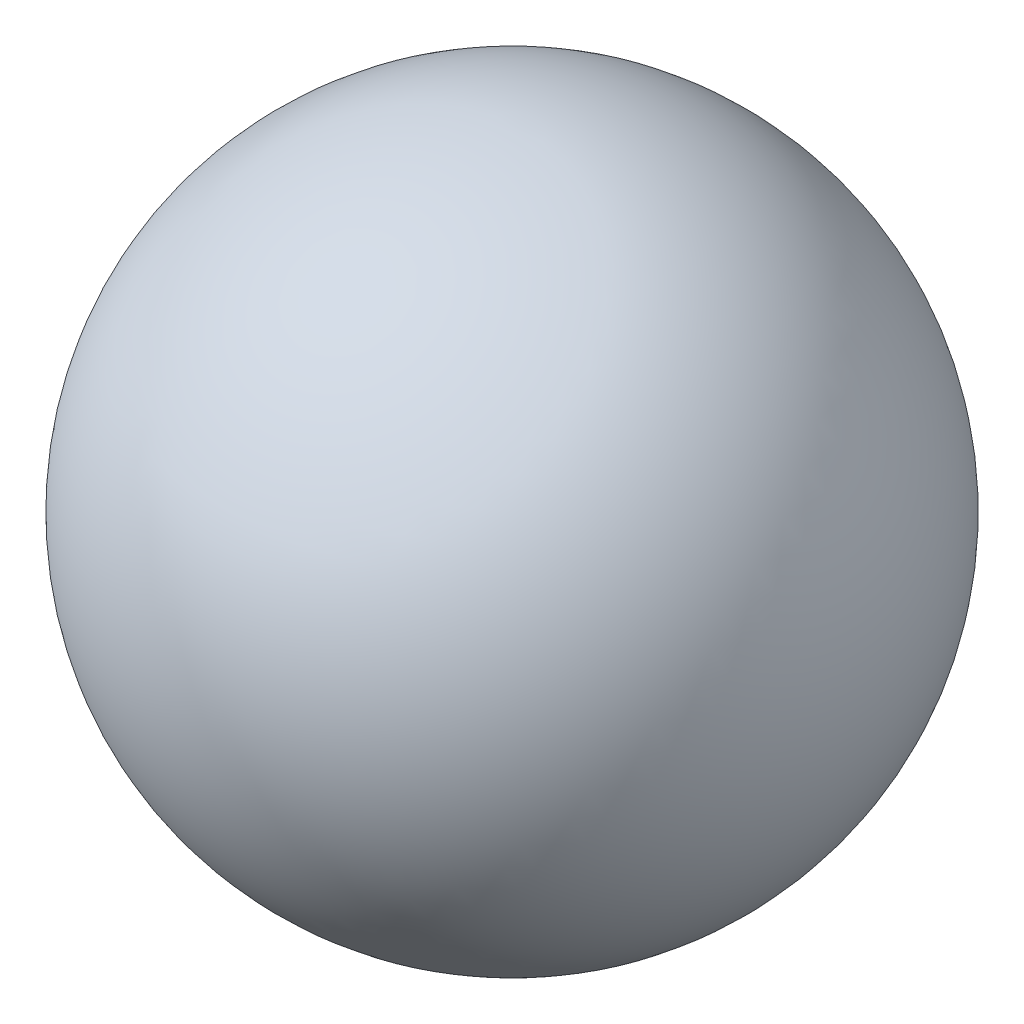
SolidWorks part; units mm, degrees
material "Silicon nitride"
ref_plane "Front Plane" through (0, 0, 0) normal (0, 0, 1) x (1, 0, 0)
ref_plane "Top Plane" through (0, 0, 0) normal (0, 1, 0) x (1, 0, 0)
ref_plane "Right Plane" through (0, 0, 0) normal (1, 0, 0) x (0, 0, -1)
ref_axis "Centre Axis" through (0, 3.9291, 0) along (0, -1, 0)
ref_axis "Revolution Axis" through (0, 0, 3.9291) along (0, 0, -1)
sketch "Sketch1" plane through (0, 0, 0) normal (0, 0, 1) x (1, 0, 0)
  line L0 (0, 3.5719) -> (0, -3.5719)
  line L2 (55, 0) -> (-55, 0) construction
  line L3 (0, 3.9291) -> (0, -3.9291) construction
  arc A0 (0, 3.5719) -> (0, -3.5719) centre (0, 0) ccw
  arc A1 (0, -3.5719) -> (0, 3.5719) centre (0, 0) ccw construction
  dimension "D1" = 7.1437
revolve "Revolve1" add sketch "Sketch1" angle 360 about axis through (0, 3.9291, 0) along (0, -1, 0)
